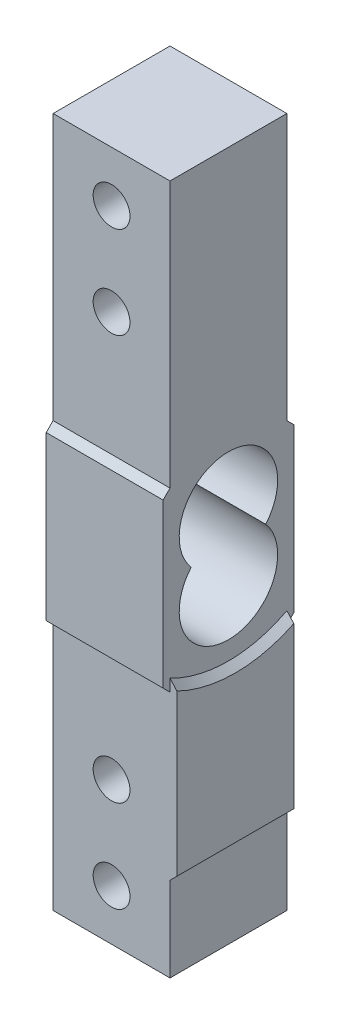
SolidWorks part; units mm, degrees
ref_plane "Front Plane" through (0, 0, 0) normal (0, 0, 1) x (1, 0, 0)
ref_plane "Top Plane" through (0, 0, 0) normal (0, 1, 0) x (1, 0, 0)
ref_plane "Right Plane" through (0, 0, 0) normal (1, 0, 0) x (0, 0, -1)
ref_axis "X Axis" through (-88.99, 0, 0) along (1, 0, 0)
ref_axis "Y Axis" through (0, 55, 0) along (0, -1, 0)
ref_axis "Z Axis" through (0, 0, -88.99) along (0, 0, 1)
sketch "Sketch1" plane through (0, 0, 0) normal (0, 1, 0) x (1, 0, 0)
  line L1 (-6.35, -6.35) -> (6.35, -6.35)
  line L2 (-6.35, -6.35) -> (-6.35, 6.35)
  line L3 (-6.35, 6.35) -> (6.35, 6.35)
  line L4 (6.35, -6.35) -> (6.35, 6.35)
  line L5 (-6.35, -6.35) -> (6.35, 6.35) construction
  line L6 (-6.35, 6.35) -> (6.35, -6.35) construction
  point P0 (0, 0)
  dimension "D1" = 12.7
extrude "Boss-Extrude1" add sketch "Sketch1" along normal mid plane 75
sketch "Sketch2" plane through (0, 0, 0) normal (1, 0, 0) x (0, 0, -1)
  line L0 (-6.35, 0) -> (6.35, 0) construction
  line L1 (-6.35, 37.5) -> (-6.35, -37.5) construction
  line L2 (6.35, 37.5) -> (6.35, -37.5) construction
  arc A0 (4.0463, 0) -> (-4.0463, 0) centre (0, 3.5) ccw
  arc A1 (4.0463, 0) -> (-4.0463, 0) centre (0, -3.5) cw
  point P7 (0, 3.5)
  dimension "D1" = 7
  dimension "D2" = 1
extrude "Cut-Extrude1" cut sketch "Sketch2" against normal through all both and the other way through all
sketch "Sketch3" plane through (0, 0, 0) normal (1, 0, 0) x (0, 0, -1)
  line L0 (6.35, 37.5) -> (6.35, -37.5) construction
  line L1 (6.35, 9.85) -> (7.1, 9.85)
  line L2 (6.35, 9.85) -> (6.35, -11.85)
  line L3 (6.35, -11.85) -> (7.1, -11.85)
  line L4 (7.1, 9.85) -> (7.1, -11.85)
  line L5 (0, 8.85) -> (0, -8.85) construction
  line L6 (-7.1, 9.85) -> (-7.1, -11.85)
  line L7 (-6.35, -11.85) -> (-7.1, -11.85)
  line L8 (-6.35, 9.85) -> (-6.35, -11.85)
  line L9 (-6.35, 9.85) -> (-7.1, 9.85)
  arc A0 (4.0463, 0) -> (-4.0463, 0) centre (0, 3.5) ccw construction
  arc A1 (-4.0463, 0) -> (4.0463, 0) centre (0, -3.5) ccw construction
  dimension "D1" = 1
  dimension "D2" = 3
  dimension "D3" = 0.75
extrude "Boss-Extrude2" add sketch "Sketch3" along normal up to surface (6.35 mm away) from surface up to face at (6.35, 0, 0) starting at face at (-6.35, 0, 0)
sketch "Sketch4" plane through (6.35, 0, 0) normal (1, 0, 0) x (0, 0, -1)
  line L0 (6.35, -11.85) -> (6.35, -37.5) construction
  line L2 (-6.35, -7.85) -> (-6.35, -29.55)
  line L3 (-6.35, -29.55) -> (6.35, -29.55)
  line L4 (6.35, -7.85) -> (6.35, -29.55)
  line L5 (-6.35, -11.85) -> (-6.35, -37.5) construction
  line L6 (7.1, 9.85) -> (7.1, -11.85) construction
  arc A0 (-6.35, -7.85) -> (6.35, -7.85) centre (0, 2.7957) ccw
  arc A1 (-4.0463, 0) -> (4.0463, 0) centre (0, -3.5) ccw construction
  point P12 (0, -8.85)
  point P15 (6.35, -7.7711)
  point P16 (6.35, -7.8133)
  dimension "D1" = 0.75
  dimension "D2" = 1
extrude "Boss-Extrude3" add sketch "Sketch4" along normal blind 0.75
chamfer "Chamfer1" distance 2 angle 45 6 edges at (7.1, -29.55, 0) (7.1, -9.6, 0) (0, -11.85, -7.1) (0, 9.85, -7.1) (0, 9.85, 7.1) (0, -11.85, 7.1)
sketch "Sketch5" plane through (0, 0, 0) normal (0, 0, 1) x (1, 0, 0)
  line L0 (-6.35, 0) -> (6.35, 0) construction
  line L1 (6.35, -9.85) -> (6.35, 7.85) construction
  line L2 (0, 37.5) -> (0, -37.5) construction
  line L3 (-6.35, 37.5) -> (6.35, 37.5) construction
  line L4 (-6.35, -37.5) -> (6.35, -37.5) construction
  circle A0 centre (0, 32) radius 2
  circle A1 centre (0, 22) radius 2
  circle A2 centre (0, -32) radius 2
  circle A3 centre (0, -22) radius 2
  dimension "D3" = 4
  dimension "D1" = 44
  dimension "D2" = 64
extrude "Cut-Extrude2" cut sketch "Sketch5" against normal through all both and the other way through all
